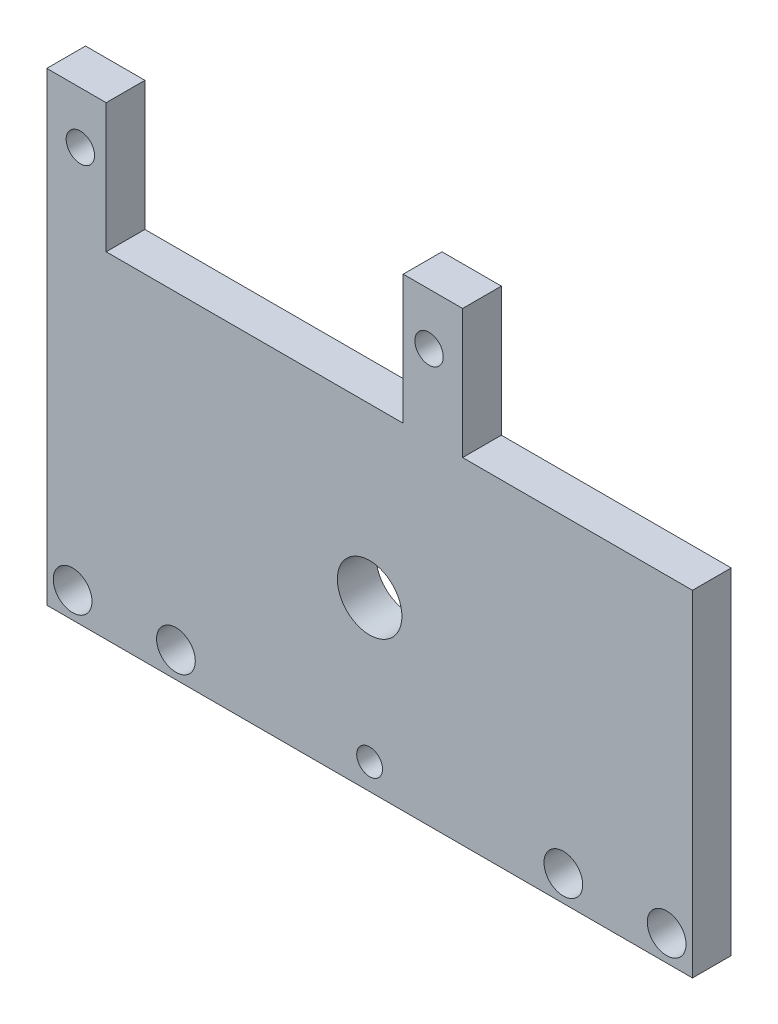
SolidWorks part; units mm, degrees
ref_plane "Front" through (0, 0, 0) normal (0, 0, 1) x (1, 0, 0)
ref_plane "Top" through (0, 0, 0) normal (0, 1, 0) x (1, 0, 0)
ref_plane "Right" through (0, 0, 0) normal (1, 0, 0) x (0, 0, -1)
sketch "Эскиз1" plane through (0, 0, 0) normal (0, 0, 1) x (1, 0, 0)
  line L0 (-12.4103, 7.3513) -> (-12.4103, -5.6487) construction
  line L2 (-37.4103, -18.6487) -> (12.5897, -18.6487)
  line L3 (-37.4103, -18.6487) -> (-37.4103, 7.3513)
  line L4 (-32.8103, 7.3513) -> (-9.8103, 7.3513)
  line L5 (12.5897, -18.6487) -> (12.5897, 7.3513)
  line L6 (-12.4103, -18.6487) -> (-12.4103, -5.6487) construction
  line L8 (-37.4103, 7.3513) -> (-37.4103, 17.3513)
  line L9 (-37.4103, 17.3513) -> (-32.8103, 17.3513)
  line L10 (-32.8103, 7.3513) -> (-32.8103, 17.3513)
  line L11 (-5.2103, 7.3513) -> (12.5897, 7.3513)
  line L13 (-9.8103, 7.3513) -> (-9.8103, 17.3513)
  line L14 (-9.8103, 17.3513) -> (-5.2103, 17.3513)
  line L15 (-5.2103, 7.3513) -> (-5.2103, 17.3513)
  circle A0 centre (-12.4103, -5.6487) radius 2.5
  circle A1 centre (-34.8103, 13.3513) radius 1.1
  circle A2 centre (-7.8103, 13.3513) radius 1.1
  circle A3 centre (-35.4103, -16.6487) radius 1.5
  circle A4 centre (10.5897, -16.6487) radius 1.5
  circle A6 centre (-12.4103, -16.6487) radius 1
  circle A7 centre (-27.4103, -16.6487) radius 1.5
  circle A8 centre (2.5897, -16.6487) radius 1.5
  dimension "D3" = 5
  dimension "D5" = 4.6
  dimension "D2" = 50
  dimension "D7" = 4
  dimension "D9" = 23
  dimension "D13" = 2
  dimension "D15" = 2
  dimension "D17" = 2
  dimension "D18" = 8
  dimension "D19" = 8
  dimension "D4" = 13
  dimension "D6" = 10
  dimension "D8" = 4.6
  dimension "D10" = 2
  dimension "D11" = 2
  dimension "D12" = 26
  dimension "D14" = 2
  dimension "D16" = 2
extrude "Бобышка-Вытянуть1" add sketch "Эскиз1" along normal blind 3
